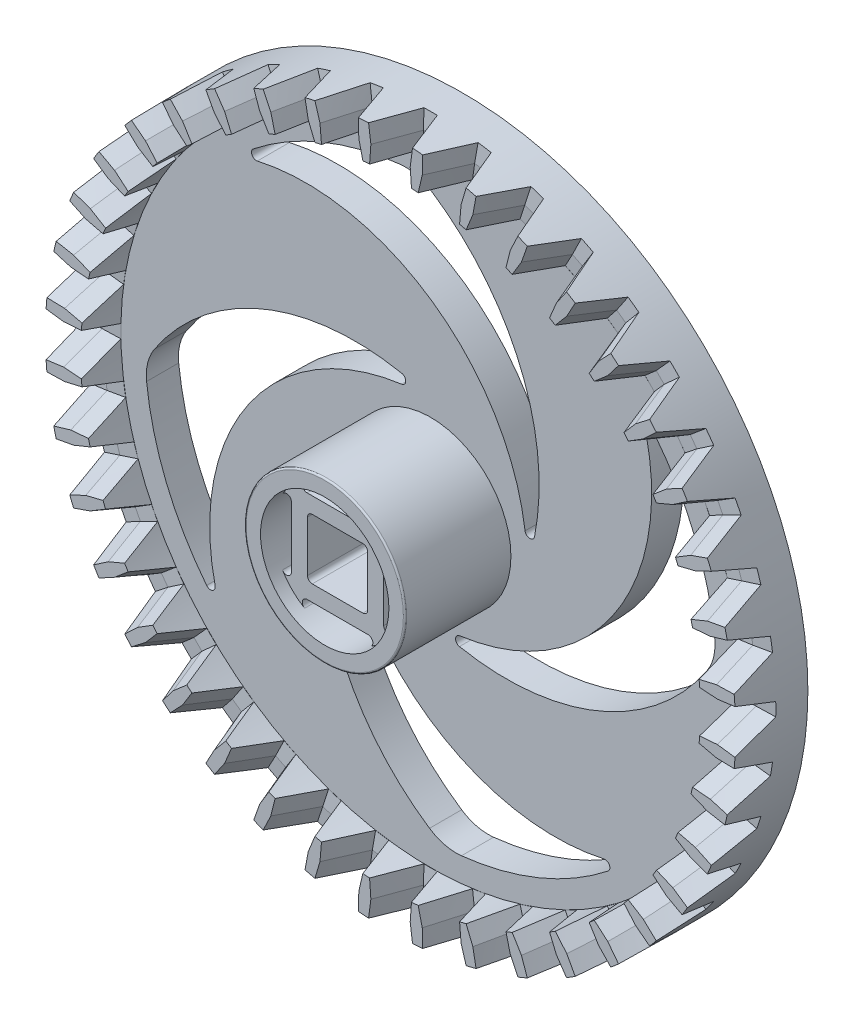
SolidWorks part; units mm, degrees
ref_plane "Front Plane" through (0, 0, 0) normal (0, 0, 1) x (1, 0, 0)
ref_plane "Top Plane" through (0, 0, 0) normal (0, 1, 0) x (1, 0, 0)
ref_plane "Right Plane" through (0, 0, 0) normal (1, 0, 0) x (0, 0, -1)
sketch "Sketch1" plane through (0, 0, 0) normal (0, 0, 1) x (1, 0, 0)
  circle A0 centre (0, 0) radius 21.5
  dimension "D1" = 43
extrude "Boss-Extrude1" add sketch "Sketch1" along normal blind 3.4
sketch "Sketch2" plane through (0, 0, 0) normal (0, 0, 1) x (1, 0, 0)
  line L1 (-1.875, -1.875) -> (1.875, -1.875)
  line L2 (-1.875, -1.875) -> (-1.875, 1.875)
  line L3 (-1.875, 1.875) -> (1.875, 1.875)
  line L4 (1.875, -1.875) -> (1.875, 1.875)
  line L5 (-1.875, -1.875) -> (1.875, 1.875) construction
  line L6 (-1.875, 1.875) -> (1.875, -1.875) construction
  point P0 (0, 0)
  dimension "D1" = 3.75
extrude "Cut-Extrude2" cut sketch "Sketch2" against normal through all and the other way through all
sketch "Sketch3" plane through (0, 0, 3.4) normal (0, 0, 1) x (1, 0, 0)
  line L0 (0, 0) -> (0, 38.7967) construction
sketch "Sketch4" plane through (0, 0, 3.4) normal (0, 0, 1) x (1, 0, 0)
  circle A0 centre (0, 0) radius 21.5 construction
  circle A1 centre (0, 0) radius 21.5
  circle A2 centre (0, 0) radius 19.3
  dimension "D1" = 2.2
extrude "Boss-Extrude2" add sketch "Sketch4" along normal blind 2.5
ref_plane "Plane1" through (0, 21.5, 0) normal (0, 1, 0) x (1, 0, 0)
sketch "Sketch5" plane through (0, 0, 5.9) normal (0, 0, 1) x (1, 0, 0)
  line L0 (-1.375, 21.456) -> (-1.225, 20.3632)
  line L1 (-1.225, 20.3632) -> (-1.305, 19.2558)
  line L2 (0, 0) -> (0, 38.7967) construction
  line L3 (0, 0) -> (0, 21.4952) construction
  line L4 (1.375, 21.456) -> (1.225, 20.3632)
  line L5 (1.225, 20.3632) -> (1.305, 19.2558)
  line L6 (-0.415, 21.496) -> (-0.35, 20.397)
  line L7 (-0.35, 20.397) -> (-0.415, 19.2955)
  line L8 (0.415, 21.496) -> (0.35, 20.397)
  line L9 (0.35, 20.397) -> (0.415, 19.2955)
  line L10 (-0.415, 19.2955) -> (0.415, 19.2955)
  line L11 (-1.305, 19.2558) -> (1.305, 19.2558)
  line L12 (-0.35, 20.397) -> (0.35, 20.397)
  line L13 (-1.225, 20.3632) -> (1.225, 20.3632)
  line L14 (-0.415, 21.496) -> (0.415, 21.496)
  line L15 (-1.375, 21.456) -> (1.375, 21.456)
  line L16 (-0.415, 21.496) -> (-0.415, 19.2955) construction
  line L17 (0.415, 19.2955) -> (0.415, 21.496) construction
  circle A0 centre (0, 0) radius 20.4
  circle A1 centre (0, 0) radius 21.5 construction
  circle A2 centre (0, 0) radius 19.3 construction
  dimension "D1" = 1.1
  dimension "D2" = 1.1
  dimension "D3" = 0.83
  dimension "D4" = 0.7
  dimension "D5" = 2.45
  dimension "D6" = 2.61
  dimension "D7" = 2.75
ref_plane "Plane2" through (0, 20.3632, 0) normal (0, 1, 0) x (1, 0, 0)
ref_plane "Plane3" through (0, 19.2558, 0) normal (0, 1, 0) x (1, 0, 0)
sketch "Sketch6" plane through (0, 19.2558, 0) normal (0, 1, 0) x (1, 0, 0)
  line L0 (-19.3, -3.4) -> (19.3, -3.4) construction
  line L1 (-19.3, -3.4) -> (19.3, -3.4) construction
  line L2 (-1.305, -5.9) -> (1.305, -5.9) construction
  line L3 (-1.305, -5.9) -> (1.305, -5.9)
  line L4 (-0.415, -5.9) -> (0.415, -5.9) construction
  line L5 (-0.415, -5.9) -> (0.415, -5.9) construction
  line L6 (-0.415, -5.9) -> (-1.305, -3.4) construction
  line L7 (-1.305, -3.4) -> (1.305, -3.4) construction
  line L8 (1.305, -3.4) -> (0.415, -5.9) construction
  line L9 (1.305, -5.9) -> (1.305, -3.4) construction
  line L10 (-1.305, -5.9) -> (-1.305, -3.4) construction
  line L11 (-0.415, -5.9) -> (-0.415, -3.4) construction
  line L12 (0.415, -5.9) -> (0.415, -3.4) construction
  line L13 (-1.305, -5.9) -> (-0.415, -3.4)
  line L14 (-0.415, -3.4) -> (0.415, -3.4)
  line L15 (0.415, -3.4) -> (1.305, -5.9)
sketch "Sketch7" plane through (0, 20.3632, 0) normal (0, 1, 0) x (1, 0, 0)
  line L0 (-19.3, -3.4) -> (19.3, -3.4) construction
  line L1 (-19.3, -3.4) -> (19.3, -3.4) construction
  line L2 (-0.35, -5.9) -> (0.35, -5.9) construction
  line L3 (-0.35, -5.9) -> (0.35, -5.9) construction
  line L4 (-1.225, -5.9) -> (1.225, -5.9) construction
  line L5 (-1.225, -5.9) -> (1.225, -5.9)
  line L6 (-6.5705, -3.5) -> (3.8306, -3.5) construction
  line L7 (-1.225, -5.9) -> (-1.225, -2.6306) construction
  line L8 (1.225, -5.9) -> (1.225, -2.6306) construction
  line L9 (-0.35, -5.9) -> (-1.225, -3.5) construction
  line L10 (-1.225, -3.5) -> (1.225, -3.5) construction
  line L11 (1.225, -3.5) -> (0.35, -5.9) construction
  line L12 (-0.35, -5.9) -> (-0.35, -2.7923) construction
  line L13 (0.35, -5.9) -> (0.35, -2.7923) construction
  line L14 (-1.225, -5.9) -> (-0.35, -3.5)
  line L15 (-0.35, -3.5) -> (0.35, -3.5)
  line L16 (0.35, -3.5) -> (1.225, -5.9)
  dimension "D1" = 0.1
sketch "Sketch8" plane through (0, 21.5, 0) normal (0, 1, 0) x (1, 0, 0)
  line L0 (-19.3, -3.4) -> (19.3, -3.4) construction
  line L1 (-19.3, -3.4) -> (19.3, -3.4) construction
  line L2 (-0.415, -5.9) -> (0.415, -5.9) construction
  line L3 (-0.415, -5.9) -> (0.415, -5.9) construction
  line L4 (-1.375, -5.9) -> (1.375, -5.9) construction
  line L5 (-1.375, -5.9) -> (1.375, -5.9)
  line L6 (-1.375, -5.9) -> (-1.375, -3.043) construction
  line L7 (1.375, -5.9) -> (1.375, -3.2635) construction
  line L8 (-0.415, -5.9) -> (-1.375, -3.4) construction
  line L9 (-1.375, -3.4) -> (1.375, -3.4) construction
  line L10 (1.375, -3.4) -> (0.415, -5.9) construction
  line L11 (-0.415, -5.9) -> (-0.415, -2.818) construction
  line L12 (0.415, -5.9) -> (0.415, -2.818) construction
  line L13 (-1.375, -5.9) -> (-0.415, -3.4)
  line L14 (-0.415, -3.4) -> (0.415, -3.4)
  line L15 (0.415, -3.4) -> (1.375, -5.9)
loft "Cut-Loft2" cut profiles "Sketch6", "Sketch7" start constraint default connector at (-1.305, 19.2558, 5.9) connector at (-1.225, 20.3632, 5.9)
loft "Cut-Loft4" cut profiles "Sketch7<2>", "Sketch8" connector at (-1.225, 20.3632, 5.9) connector at (-1.375, 21.5, 5.9)
sketch "Sketch7<2>" plane through (0, 20.3632, 0) normal (0, 1, 0) x (1, 0, 0) same geometry as "Sketch7"
pattern_circular "CirPattern1" count 40 over 360 about axis through (0, 0, 0) along (0, 0, 1) of "Cut-Loft2", "Cut-Loft4"
sketch "Sketch9" plane through (0, 0, 3.4) normal (0, 0, 1) x (1, 0, 0)
  line L5 (1.875, -1.875) -> (1.875, 1.875)
  line L6 (-1.875, -1.875) -> (1.875, -1.875)
  line L7 (-1.875, 1.875) -> (-1.875, -1.875)
  line L8 (1.875, 1.875) -> (-1.875, 1.875)
  line L9 (1.875, -1.875) -> (1.875, 1.875)
  line L10 (-1.875, -1.875) -> (1.875, -1.875)
  line L11 (-1.875, 1.875) -> (-1.875, -1.875)
  line L12 (1.875, 1.875) -> (-1.875, 1.875)
  circle A0 centre (0, 0) radius 5
  dimension "D2" = 10
  dimension "D1" = 0
extrude "Boss-Extrude3" add sketch "Sketch9" along normal offset from surface (6.6 mm away) 10 up to face at (0, 0, 0)
sketch "Sketch10" plane through (0, 0, 0) normal (0, 0, -1) x (-1, 0, 0)
  circle A0 centre (0, 0) radius 21.5 construction
  circle A1 centre (0, 0) radius 21.5
extrude "Cut-Extrude3" cut sketch "Sketch10" against normal offset from surface (1.4 mm away) 2 up to face at (19.3, 0, 3.4)
sketch "Sketch11" plane through (0, 0, 1.4) normal (0, 0, -1) x (-1, 0, 0)
  circle A0 centre (0, 0) radius 5
  circle A2 centre (0, 0) radius 4
  dimension "D1" = 10
  dimension "D2" = 8
extrude "Boss-Extrude4" add sketch "Sketch11" along normal offset from surface (1.4 mm away) 10 up to face at (0, 0, 10)
sketch "Sketch12" plane through (0, 0, 1.4) normal (0, 0, -1) x (-1, 0, 0)
  line L1 (2.875, 2.875) -> (-2.875, 2.875)
  line L2 (-2.875, 2.875) -> (-2.875, -2.875)
  line L3 (-2.875, -2.875) -> (2.875, -2.875)
  line L4 (2.875, -2.875) -> (2.875, 2.875)
  line L5 (1.875, 1.875) -> (-1.875, 1.875)
  line L6 (1.875, -1.875) -> (1.875, 1.875)
  line L7 (-1.875, -1.875) -> (1.875, -1.875)
  line L8 (-1.875, 1.875) -> (-1.875, -1.875)
  line L9 (1.875, 1.875) -> (-1.875, 1.875)
  line L10 (1.875, -1.875) -> (1.875, 1.875)
  line L11 (-1.875, -1.875) -> (1.875, -1.875)
  line L12 (-1.875, 1.875) -> (-1.875, -1.875)
  dimension "D1" = 0
  dimension "D2" = 1
extrude "Boss-Extrude5" add sketch "Sketch12" along normal offset from surface (0.6 mm away) 0.8 up to face at (4, 0, 0)
sketch "Sketch13" plane through (0, 0, 10) normal (0, 0, 1) x (1, 0, 0)
  line L9 (2.875, 2.875) -> (-2.875, 2.875)
  line L10 (2.875, -2.875) -> (2.875, 2.875)
  line L11 (-2.875, -2.875) -> (2.875, -2.875)
  line L12 (-2.875, 2.875) -> (-2.875, -2.875)
  line L13 (2.875, 2.875) -> (-2.875, 2.875)
  line L14 (2.875, -2.875) -> (2.875, 2.875)
  line L15 (-2.875, -2.875) -> (2.875, -2.875)
  line L16 (-2.875, 2.875) -> (-2.875, -2.875)
  circle A0 centre (0, 0) radius 4
  dimension "D2" = 8
  dimension "D1" = 1
extrude "Cut-Extrude4" cut sketch "Sketch13" against normal up to surface (6.6 mm away) contours L13 A0 | L16 A0 | L14 A0 | L15 A0 region at (0, 3.3309, 10) region at (3.3309, 0, 10) region at (-3.3309, 0, 10) region at (0, -3.3309, 10) up to face at (19.3, 0, 3.4)
sketch "Sketch14" plane through (0, 0, 10) normal (0, 0, 1) x (1, 0, 0)
  arc A0 (2.7811, 2.875) -> (-2.7811, 2.875) centre (0, 0) ccw construction
  circle A1 centre (0, 0) radius 4
extrude "Cut-Extrude5" cut sketch "Sketch14" against normal blind 0.8
fillet "Fillet1" radius 0.3 20 edges at (2.875, 2.7811, 1.1) (2.875, -2.7811, 1.1) (2.7811, -2.875, 1.1) (-2.7811, -2.875, 1.1) (-2.875, -2.7811, 1.1) (-2.875, 2.7811, 1.1) (-2.7811, 2.875, 1.1) (2.7811, 2.875, 1.1) (-2.7811, -2.875, 6.3) (-2.875, -2.7811, 6.3) (-2.875, 2.7811, 6.3) (-2.7811, 2.875, 6.3) (2.875, 2.7811, 6.3) (2.875, -2.7811, 6.3) (2.7811, -2.875, 6.3) (2.7811, 2.875, 6.3) (-1.875, -1.875, 5) (1.875, -1.875, 5) (-1.875, 1.875, 5) (1.875, 1.875, 5)
fillet "Fillet2" radius 0.1 2 edges at (5, 0, 0) (5, 0, 10)
sketch "Sketch15" plane through (0, 0, 1.4) normal (0, 0, -1) x (-1, 0, 0)
  line L0 (0, 0) -> (-10.6066, 10.6066) construction
  line L1 (0, 0) -> (0, 21.5) construction
  line L2 (-6.6584, 12.3153) -> (12.3153, -6.6584)
  line L3 (-12.3153, 6.6584) -> (6.6584, -12.3153)
  line L4 (-13.0224, 5.9513) -> (5.9513, -13.0224)
  line L5 (-5.9513, 13.0224) -> (13.0224, -5.9513)
  line L6 (13.0224, 5.9513) -> (-5.9513, -13.0224)
  line L7 (12.3153, 6.6584) -> (-6.6584, -12.3153)
  line L8 (6.6584, 12.3153) -> (-12.3153, -6.6584)
  line L9 (5.9513, 13.0224) -> (-13.0224, -5.9513)
  circle A0 centre (0, 0) radius 15
  circle A1 centre (0, 0) radius 14
  circle A2 centre (0, 0) radius 21.5 construction
  dimension "D1" = 30
  dimension "D2" = 1
  dimension "D3" = 45
  dimension "D4" = 4
  dimension "D5" = 4
  dimension "D6" = 1
  dimension "D7" = 1
sketch "Sketch16" plane through (0, 0, 1.4) normal (0, 0, -1) x (-1, 0, 0)
  circle A0 centre (0, 0) radius 21.5 construction
  circle A1 centre (0, 0) radius 21.5
sketch "Sketch17" plane through (0, 0, 1.4) normal (0, 0, -1) x (-1, 0, 0)
  line L0 (0, 0) -> (-31.5874, 0) construction
  line L1 (0, 0) -> (12.0827, 13.0709) construction
  line L2 (0, 0) -> (0.854, 17.7795) construction
  line L3 (0, 0) -> (0, 17.8) construction
  circle A0 centre (0, 0) radius 19.3 construction
  circle A1 centre (0, 0) radius 19.3 construction
  circle A2 centre (0, 0) radius 17.8
  circle A3 centre (0, 0) radius 6
  circle A4 centre (0, 0) radius 5 construction
  arc A5 (-6, 0) -> (0.854, 17.7795) centre (8.2647, 4.7118) cw
  arc A6 (-6, 0) -> (12.0827, 13.0709) centre (7.7655, 0) cw
  dimension "D1" = 1.5
  dimension "D2" = 1
  dimension "D3" = 2.75
  dimension "D4" = 42.75
extrude "Cut-Extrude6" cut sketch "Sketch17" against normal blind 10 contours A5 A6 A2 region at (-0.0696, 12.4657, 1.4)
pattern_circular "CirPattern2" count 4 over 360 about axis through (0, 0, 1.4) along (0, 0, -1) of "Cut-Extrude6"
fillet "Fillet3" radius 0.3 8 edges at (-12.0827, 13.0709, 2.4) (13.0709, 12.0827, 2.4) (12.0827, -13.0709, 2.4) (-13.0709, -12.0827, 2.4) (-6, 0, 2.4) (0, 6, 2.4) (0, -6, 2.4) (6, 0, 2.4)
fillet "Fillet4" radius 3 4 edges at (17.7795, 0.854, 2.4) (0.854, -17.7795, 2.4) (-17.7795, -0.854, 2.4) (-0.854, 17.7795, 2.4)
